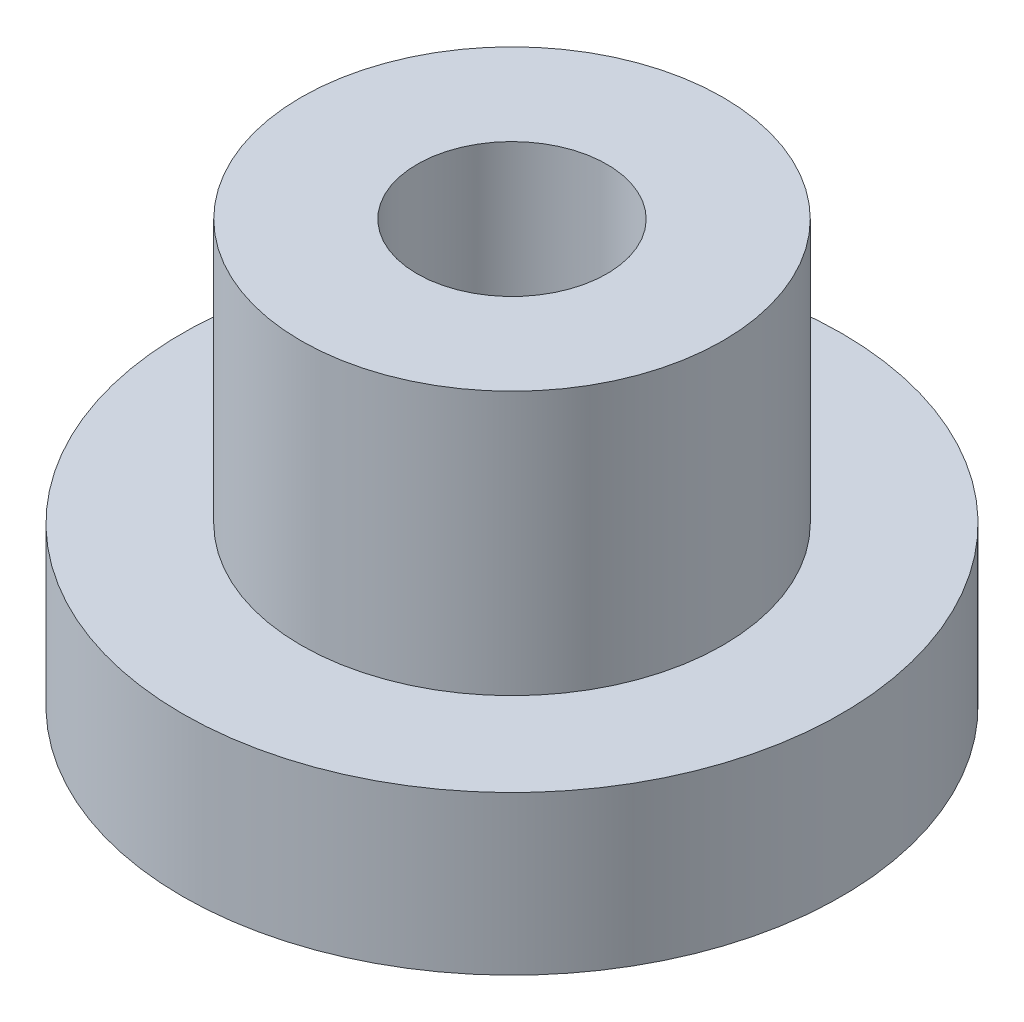
SolidWorks part; units mm, degrees
ref_plane "Płaszczyzna przednia" through (0, 0, 0) normal (0, 0, 1) x (1, 0, 0)
ref_plane "Płaszczyzna górna" through (0, 0, 0) normal (0, 1, 0) x (1, 0, 0)
ref_plane "Płaszczyzna prawa" through (0, 0, 0) normal (1, 0, 0) x (0, 0, -1)
sketch "Sketch1" plane through (0, 0, 0) normal (0, 1, 0) x (1, 0, 0)
  circle A0 centre (0, 0) radius 4
  dimension "D1" = 8
extrude "Boss-Extrude1" add sketch "Sketch1" along normal blind 5
sketch "Sketch2" plane through (0, 0, 0) normal (0, -1, 0) x (1, 0, 0)
  circle A0 centre (0, 0) radius 6.25
  dimension "D1" = 12.5
extrude "Boss-Extrude2" add sketch "Sketch2" along normal blind 3
sketch "Sketch3" plane through (0, 5, 0) normal (0, 1, 0) x (1, 0, 0)
  circle A0 centre (0, 0) radius 1.8
  dimension "D1" = 3.6
extrude "Cut-Extrude1" cut sketch "Sketch3" against normal through all
hole_wizard "CSK for M3 Hex Socket Countersunk Head Screw1" positions "Sketch4" profile "Sketch5" countersink size "M3" standard "DIN" end condition through all
sketch "Sketch4" plane through (0, -3, 0) normal (0, -1, 0) x (-1, 0, 0)
  point P0 (0, 0)
sketch "Sketch5" plane through (0, -3, 0) normal (1, 0, 0) x (0, 0, -1)
  line L0 (0, 0) -> (0, 8)
  line L1 (0, 8) -> (1.8, 8)
  line L2 (1.8, 8) -> (1.8, 1.67)
  line L3 (1.8, 1.67) -> (3.47, 0)
  line L5 (3.47, 0) -> (0, 0)
  line L6 (-1.8, 1.67) -> (-3.47, 0) construction
  line L11 (0, -6.35) -> (0, 107.95) construction
  dimension "Thru Hole Dia." = 3.6
  dimension "Thru Hole Depth" = 8
  dimension "Near C'Sink Dia." = 6.94
  dimension "Near C'Sink Angle" = 90
